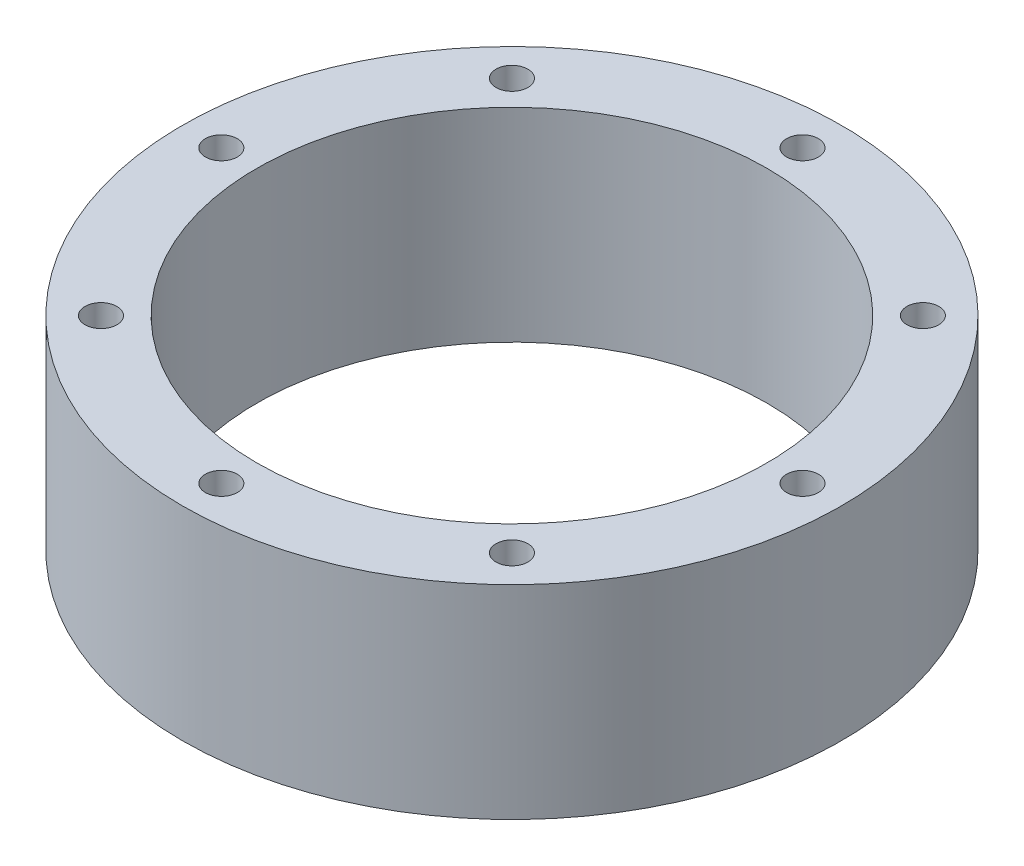
SolidWorks part; units mm, degrees
ref_plane "Front Plane" through (0, 0, 0) normal (0, 0, 1) x (1, 0, 0)
ref_plane "Top Plane" through (0, 0, 0) normal (0, 1, 0) x (1, 0, 0)
ref_plane "Right Plane" through (0, 0, 0) normal (1, 0, 0) x (0, 0, -1)
sketch "Sketch1" plane through (0, 0, 0) normal (0, 1, 0) x (1, 0, 0)
  circle A0 centre (0, 0) radius 46.5
  circle A1 centre (0, 0) radius 36
  dimension "D1" = 93
  dimension "D2" = 72
extrude "Boss-Extrude1" add sketch "Sketch1" along normal blind 28.7
sketch "Sketch2" plane through (0, 28.7, 0) normal (0, 1, 0) x (1, 0, 0)
  circle A0 centre (0, 0) radius 41 construction
  circle A1 centre (0, 41) radius 2.25
  circle A2 centre (28.9914, 28.9914) radius 2.25
  circle A3 centre (41, 0) radius 2.25
  circle A4 centre (28.9914, -28.9914) radius 2.25
  circle A5 centre (0, -41) radius 2.25
  circle A6 centre (-28.9914, -28.9914) radius 2.25
  circle A7 centre (-41, 0) radius 2.25
  circle A8 centre (-28.9914, 28.9914) radius 2.25
  point P22 (0, 0)
  dimension "D1" = 82
  dimension "D2" = 4.5
  dimension "D3" = 8
extrude "Cut-Extrude1" cut sketch "Sketch2" against normal through all
